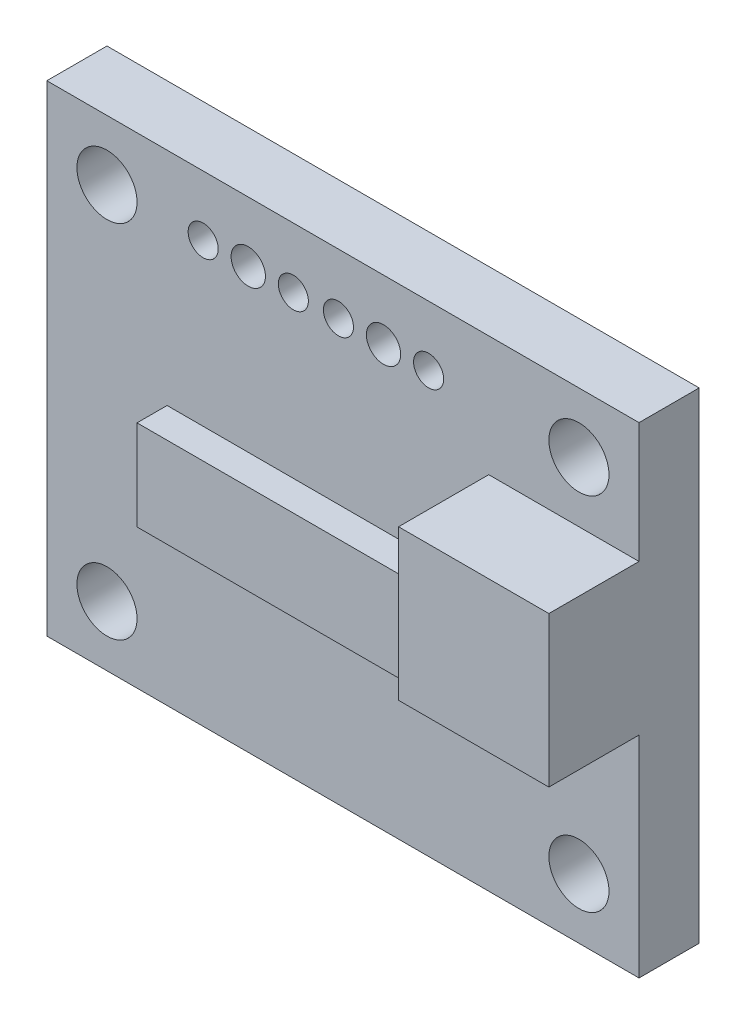
SolidWorks part; units mm, degrees
ref_plane "Front Plane" through (0, 0, 0) normal (0, 0, 1) x (1, 0, 0)
ref_plane "Top Plane" through (0, 0, 0) normal (0, 1, 0) x (1, 0, 0)
ref_plane "Right Plane" through (0, 0, 0) normal (1, 0, 0) x (0, 0, -1)
sketch "Sketch1" plane through (0, 0, 0) normal (0, 0, 1) x (1, 0, 0)
  line L0 (-16.2, 7.3563) -> (-16.2, -8.6437)
  line L1 (-16.2, -8.6437) -> (3.5, -8.6437)
  line L2 (3.5, -8.6437) -> (3.5, 7.3563)
  line L3 (3.5, 7.3563) -> (-16.2, 7.3563)
  line L4 (-1.5, -1.6437) -> (3.5, -1.6437)
  line L6 (-11.2, -8.6437) -> (-16.2, -8.6437)
  line L7 (-12.2, 0) -> (-2.2, 0)
  line L8 (-12.2, 0) -> (-12.2, -3)
  line L9 (-2.2, 0) -> (-2.2, -3)
  line L10 (-2.2, -3) -> (-12.2, -3)
  line L15 (3.5, 3.3563) -> (-1.5, 3.3563)
  line L16 (-1.5, 3.3563) -> (-1.5, -1.6437)
  line L18 (3.5, -8.6437) -> (-1.5, -8.6437)
  circle A6 centre (-11, 5.3563) radius 0.5
  circle A7 centre (-8, 5.3563) radius 0.5
  circle A8 centre (-9.5, 5.3563) radius 0.5706
  circle A9 centre (-6.5, 5.3563) radius 0.5
  circle A10 centre (-3.5, 5.3563) radius 0.5
  circle A11 centre (-5, 5.3563) radius 0.5706
  circle A72 centre (-14.2, 5.3563) radius 1
  circle A73 centre (1.5, 5.3563) radius 1
  circle A74 centre (1.5, -6.6437) radius 1
  circle A75 centre (-14.2, -6.6437) radius 1
  dimension "D15" = 1
  dimension "D20" = 1
  dimension "D80" = 4
  dimension "D173" = 2
  dimension "D178" = 2
  dimension "D182" = 2
  dimension "D5" = 2
  dimension "D2" = 19.7
  dimension "D3" = 16
  dimension "D16" = 0
  dimension "D17" = 0
  dimension "D18" = 1.5
  dimension "D19" = 1.5
  dimension "D21" = 0
  dimension "D22" = 0
  dimension "D23" = 1.5
  dimension "D24" = 1.5
  dimension "D25" = 1.5
  dimension "D26" = 0
  dimension "D43" = 2
  dimension "D158" = 7
  dimension "D162" = 10
  dimension "D163" = 3
  dimension "D167" = 5
  dimension "D171" = 2
  dimension "D172" = 2
  dimension "D174" = 2
  dimension "D175" = 2
  dimension "D176" = 2
  dimension "D177" = 2
  dimension "D180" = 4
  dimension "D181" = 2
  dimension "D183" = 2
extrude "Boss-Extrude1" add sketch "Sketch1" along normal blind 2 contours L18 L2 L16 L15 L3 L0 L6 L1 A75 A74 A73 A72 region at (-6.35, 7.1025, 0)
extrude "Boss-Extrude2" add sketch "Sketch1<3>" along normal blind 5 contours L15 L16 L4 L2 region at (1, 0.8563, 0)
sketch "Sketch1<3>" plane through (0, 0, 0) normal (0, 0, 1) x (1, 0, 0) same geometry as "Sketch1"
extrude "Boss-Extrude3" add sketch "Sketch1<4>" along normal blind 3 contours L10 L9 L7 L8 region at (-7.2, -1.5, 0)
sketch "Sketch1<4>" plane through (0, 0, 0) normal (0, 0, 1) x (1, 0, 0) same geometry as "Sketch1"
